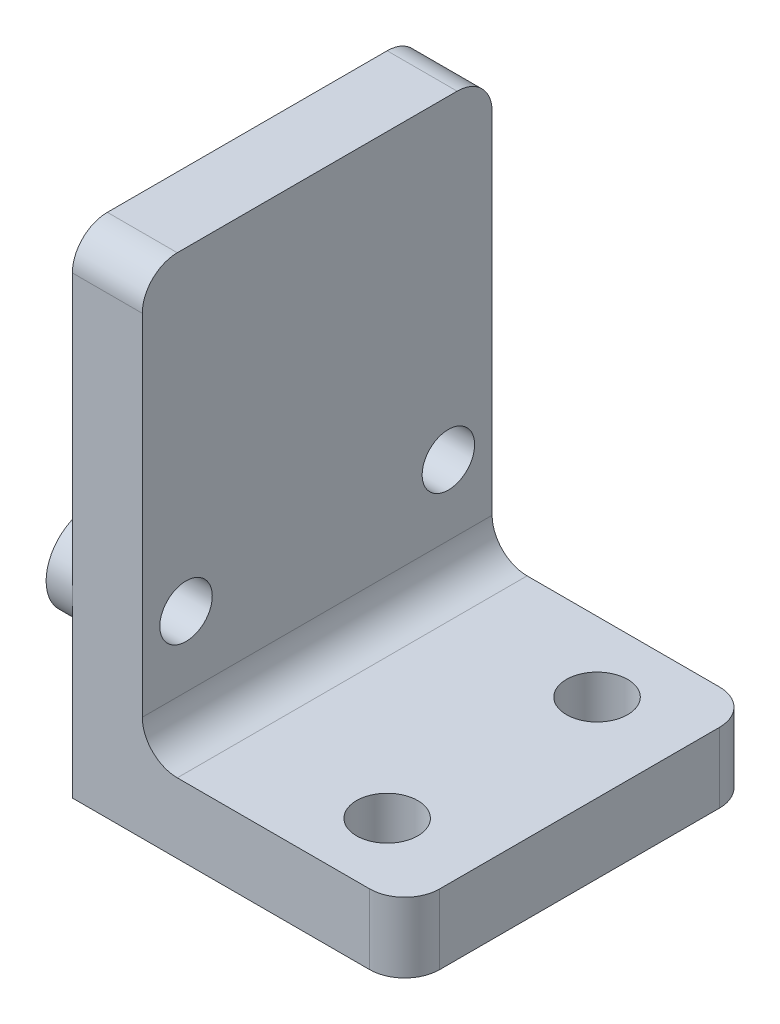
SolidWorks part; units mm, degrees
ref_plane "Front Plane" through (0, 0, 0) normal (0, 0, 1) x (1, 0, 0)
ref_plane "Top Plane" through (0, 0, 0) normal (0, 1, 0) x (1, 0, 0)
ref_plane "Right Plane" through (0, 0, 0) normal (1, 0, 0) x (0, 0, -1)
sketch "Sketch1" plane through (0, 0, 0) normal (0, 0, 1) x (1, 0, 0)
  line L0 (0, 0) -> (0, 28)
  line L1 (0, 28) -> (4, 28)
  line L2 (4, 28) -> (4, 4)
  line L3 (4, 4) -> (19, 4)
  line L4 (19, 4) -> (19, 0)
  line L5 (19, 0) -> (0, 0)
  dimension "D1" = 4
  dimension "D2" = 4
  dimension "D3" = 24
  dimension "D4" = 15
extrude "Boss-Extrude1" add sketch "Sketch1" along normal blind 20
sketch "Sketch2" plane through (0, 0, 0) normal (-1, 0, 0) x (0, 0, 1)
  line L0 (20, 28) -> (0, 28) construction
  line L1 (20, 28) -> (20, 0) construction
  circle A0 centre (17.5, 10) radius 1.5
  circle A1 centre (2.5, 10) radius 1.5
  point P4 (0, 0)
  point P9 (2, 26.5)
  point P10 (0, 0)
  dimension "D2" = 3
  dimension "D1" = 15
  dimension "D3" = 18
  dimension "D4" = 2.5
extrude "Cut-Extrude1" cut sketch "Sketch2" against normal through all
sketch "Sketch3" plane through (0, 4, 0) normal (0, 1, 0) x (1, 0, 0)
  line L0 (19, -20) -> (19, 0) construction
  circle A0 centre (14, -4) radius 1.75
  circle A1 centre (14, -16) radius 1.75
  point P6 (19, -10)
  dimension "D1" = 3.5
  dimension "D2" = 3.5
  dimension "D3" = 12
  dimension "D4" = 6
  dimension "D5" = 5
extrude "Cut-Extrude2" cut sketch "Sketch3" against normal through all
fillet "Fillet1" radius 2 5 edges at (19, 2, 0) (19, 2, 20) (4, 4, 10) (2, 28, 0) (2, 28, 20)
sketch "Sketch4" plane through (0, 0, 0) normal (-1, 0, 0) x (0, 0, 1)
  circle A0 centre (2.5, 10) radius 2.5
  circle A1 centre (17.5, 10) radius 2.5
  circle A2 centre (17.5, 10) radius 1.5 construction
  circle A3 centre (2.5, 10) radius 1.5 construction
  circle A4 centre (17.5, 10) radius 1.5
  circle A5 centre (2.5, 10) radius 1.5
extrude "Boss-Extrude2" add sketch "Sketch4" along normal blind 1.5
